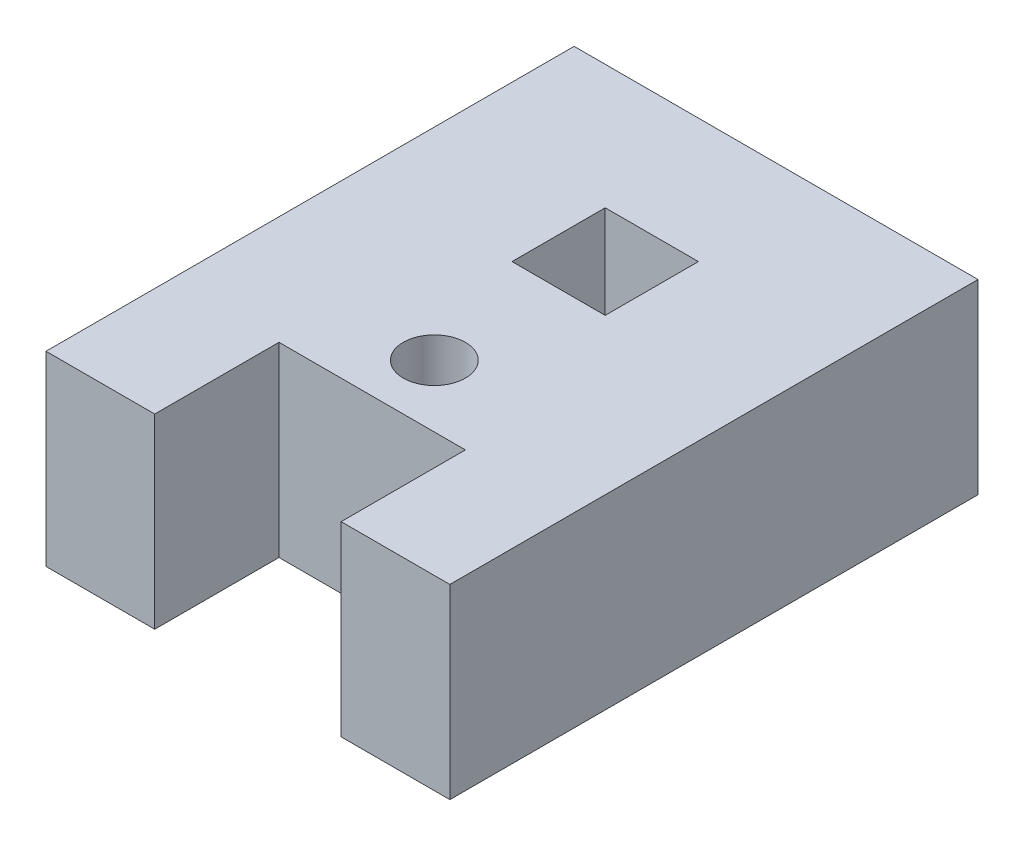
SolidWorks part; units mm, degrees
ref_plane "Front Plane" through (0, 0, 0) normal (0, 0, 1) x (1, 0, 0)
ref_plane "Top Plane" through (0, 0, 0) normal (0, 1, 0) x (1, 0, 0)
ref_plane "Right Plane" through (0, 0, 0) normal (1, 0, 0) x (0, 0, -1)
sketch "Sketch1" plane through (0, 0, 0) normal (0, 1, 0) x (1, 0, 0)
  line L0 (3.5, 0) -> (3.5, 4)
  line L1 (0, 0) -> (3.5, 0)
  line L2 (0, 0) -> (0, 17)
  line L3 (0, 17) -> (13, 17)
  line L4 (13, 0) -> (13, 17)
  line L5 (3.5, 4) -> (9.5, 4)
  line L6 (9.5, 4) -> (9.5, 0)
  line L7 (9.5, 0) -> (13, 0)
  dimension "D1" = 13
  dimension "D2" = 13
  dimension "D3" = 4
  dimension "D4" = 6
  dimension "D5" = 3.5
extrude "Boss-Extrude1" add sketch "Sketch1" along normal blind 6
sketch "Sketch2" plane through (0, 6, 0) normal (0, 1, 0) x (1, 0, 0)
  line L0 (3.5, 4) -> (9.5, 4) construction
  line L1 (5, 13) -> (8, 13)
  line L2 (5, 13) -> (5, 10)
  line L3 (5, 10) -> (8, 10)
  line L4 (8, 13) -> (8, 10)
  line L6 (13, 17) -> (0, 17) construction
  circle A0 centre (6.5, 6) radius 1
  point P8 (5, 11.5)
  point P11 (6.5, 10)
  point P12 (6.5, 4)
  point P13 (6.5, 13)
  dimension "D3" = 2
  dimension "D1" = 3
  dimension "D2" = 3
  dimension "D4" = 2
  dimension "D5" = 4
extrude "Cut-Extrude1" cut sketch "Sketch2" against normal through all
